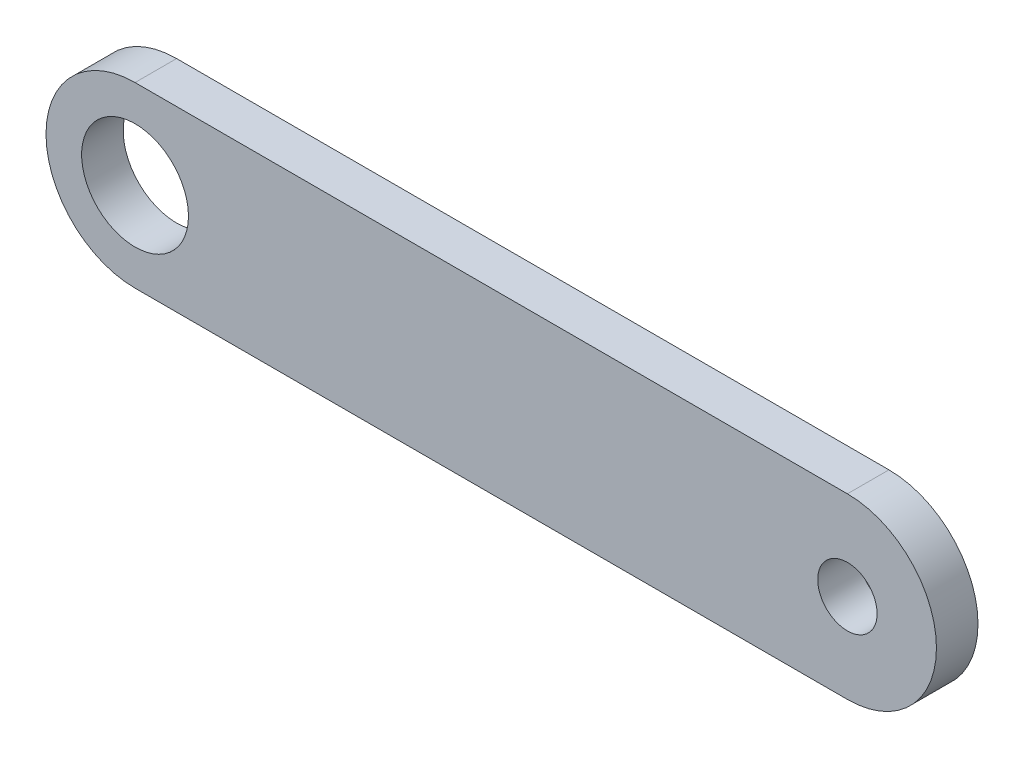
SolidWorks part; units mm, degrees
material "普通碳钢"
ref_plane "前视基准面" through (0, 0, 0) normal (0, 0, 1) x (1, 0, 0)
ref_plane "上视基准面" through (0, 0, 0) normal (0, 1, 0) x (1, 0, 0)
ref_plane "右视基准面" through (0, 0, 0) normal (1, 0, 0) x (0, 0, -1)
sketch "草图1" plane through (0, 0, 0) normal (0, 0, 1) x (1, 0, 0)
  line L0 (30, 0) -> (-30, 0) construction
  line L1 (30, 7.5) -> (-30, 7.5)
  line L2 (30, -7.5) -> (-30, -7.5)
  circle A0 centre (30, 0) radius 2.5
  circle A1 centre (-30, 0) radius 4.5
  arc A2 (30, 7.5) -> (30, -7.5) centre (30, 0) cw
  arc A3 (-30, 7.5) -> (-30, -7.5) centre (-30, 0) ccw
  point P2 (0, 0)
  dimension "D2" = 9
  dimension "D3" = 5
  dimension "D1" = 60
  dimension "D4" = 7.5
extrude "凸台-拉伸1" add sketch "草图1" along normal blind 3.5
